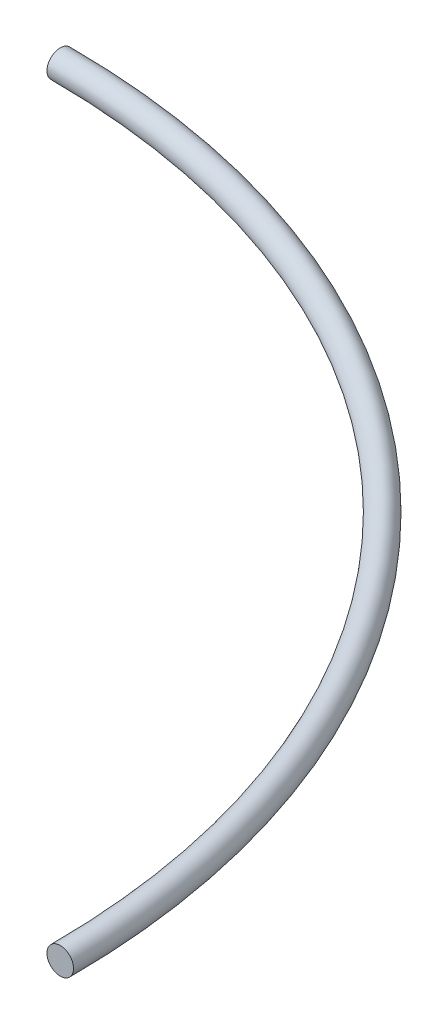
SolidWorks part; units mm, degrees
material "AISI 1020"
ref_plane "Front Plane" through (0, 0, 0) normal (0, 0, 1) x (1, 0, 0)
ref_plane "Top Plane" through (0, 0, 0) normal (0, 1, 0) x (1, 0, 0)
ref_plane "Right Plane" through (0, 0, 0) normal (1, 0, 0) x (0, 0, -1)
sketch "Sketch1" plane through (0, 0, 0) normal (0, 0, 1) x (1, 0, 0)
  line L0 (0, 0) -> (1460, 0)
  line L1 (0, 0) -> (0, 929.7724) construction
  circle A0 centre (1460, 0) radius 25
revolve "Revolve1" add sketch "Sketch1" angle 90 about L1
